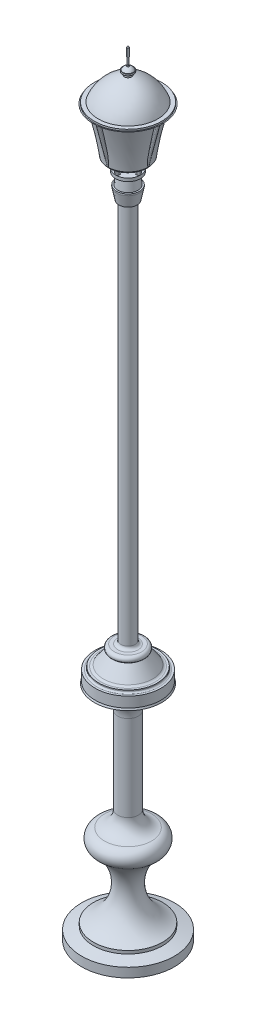
SolidWorks part; units mm, degrees
ref_plane "Front Plane" through (0, 0, 0) normal (0, 0, 1) x (1, 0, 0)
ref_plane "Top Plane" through (0, 0, 0) normal (0, 1, 0) x (1, 0, 0)
ref_plane "Right Plane" through (0, 0, 0) normal (1, 0, 0) x (0, 0, -1)
sketch "Sketch1" plane through (0, 0, 0) normal (0, 0, 1) x (1, 0, 0)
  line L0 (0, 0) -> (0, 250) construction
  line L1 (0, 0) -> (-15, 0)
  line L2 (-15, 0) -> (-15, 3)
  line L3 (-15, 3) -> (-11.1715, 4)
  line L4 (-11.1715, 4) -> (-11.1715, 5)
  line L5 (-3.3417, 64.4617) -> (-3.3417, 36.7043)
  line L6 (-10.8822, 72.0027) -> (-10.6514, 72.5731)
  line L7 (-10.6514, 72.5731) -> (-10.6514, 75.9363)
  line L8 (-10.6514, 75.9363) -> (-9.9773, 75.9363)
  line L9 (-9.4473, 76.4663) -> (-9.4473, 76.7932)
  line L10 (-9.4473, 76.7932) -> (-8.8027, 76.7932)
  line L11 (-5.0647, 81.2612) -> (-7.992, 77.2077)
  line L12 (-4.4341, 83.0374) -> (-3.3006, 83.0374)
  line L13 (-2.3006, 84.0374) -> (-2.3006, 207.5309)
  line L14 (-2.3006, 207.5309) -> (-2.9601, 207.5309)
  line L15 (-2.9601, 207.5309) -> (-3.73, 211.2793)
  line L16 (-3.73, 211.2793) -> (-3.73, 211.7765)
  line L17 (-3.73, 211.7765) -> (-3.236, 211.7765)
  line L18 (-3.236, 211.7765) -> (-2.8892, 215.4171)
  line L19 (-2.8892, 215.4171) -> (0, 215.4171)
  line L20 (0, 0) -> (0, 215.4171)
  arc A0 (-11.1715, 5) -> (-8.8506, 26.2034) centre (-16.0559, 16.2634) ccw
  arc A1 (-7.6215, 31.5849) -> (-3.3417, 36.7043) centre (-8.5434, 36.7043) ccw
  arc A2 (-7.6215, 31.5849) -> (-8.8506, 26.2034) centre (-7.0899, 28.6324) ccw
  arc A3 (-3.3417, 64.4617) -> (-10.8822, 72.0027) centre (-10.8826, 64.4617) ccw
  arc A4 (-3.3006, 83.0374) -> (-2.3006, 84.0374) centre (-3.3006, 84.0374) ccw
  arc A5 (-7.992, 77.2077) -> (-8.8027, 76.7932) centre (-8.8027, 77.7932) cw
  arc A6 (-9.4473, 76.4663) -> (-9.9773, 75.9363) centre (-9.9773, 76.4663) cw
  arc A7 (-4.4341, 83.0374) -> (-5.0647, 81.2612) centre (-4.4341, 82.0374) ccw
  dimension "D6" = 3
  dimension "D7" = 1
  dimension "D8" = 1
  dimension "D9" = 0.53
  dimension "D10" = 1
  dimension "D1" = 250
  dimension "D2" = 15
  dimension "D3" = 3
  dimension "D4" = 1
  dimension "D5" = 1
  dimension "D11" = 5
revolve "Revolve1" add sketch "Sketch1" angle 360 about L0
sketch "Sketch2" plane through (0, 215.4171, 0) normal (0, 1, 0) x (1, 0, 0)
  circle A0 centre (0, 0) radius 4
  dimension "D1" = 8
extrude "Boss-Extrude1" add sketch "Sketch2" along normal blind 1 contours A0
sketch "Sketch3" plane through (0, 0, 0) normal (1, 0, 0) x (0, 0, -1)
  line L0 (-4, 216.4171) -> (-2.9788, 216.4171)
  line L1 (-4, 216.4171) -> (-4.6212, 219.4171)
  line L2 (-2.9788, 216.4171) -> (-3.6, 219.4171)
  line L3 (-4.6212, 219.4171) -> (-3.6, 219.4171)
  line L4 (4, 216.4171) -> (-4, 216.4171) construction
  dimension "D1" = 3
  dimension "D2" = 1
extrude "Boss-Extrude2" add sketch "Sketch3" along normal mid plane 1 separate body
fillet "Fillet3" 2 edges at (0.5, 217.9171, 4.3106) (-0.5, 217.9171, 4.3106) type full round first side face at (0.5, 217.9171, 3.8) second side face at (-0.5, 217.9171, 3.8) middle face at (0, 217.9171, 4.3106)
pattern_circular "CirPattern1" count 4 over 360 about axis through (0, 216.4171, 0) along (0, 1, 0) of bodies 103
sketch "Sketch5" plane through (0, 0, 0) normal (0, 0, 1) x (1, 0, 0)
  line L0 (0, 253.7461) -> (0, 207.5309) construction
  line L1 (-2.3006, 207.5309) -> (2.3006, 207.5309) construction
  line L2 (0, 219.4171) -> (-6.1343, 219.4171)
  line L3 (0.5, 219.4171) -> (-0.5, 219.4171) construction
  line L4 (-6.1343, 219.4171) -> (-6.5254, 219.9171)
  line L5 (-6.5254, 219.9171) -> (-0.25, 219.9171)
  line L6 (-0.25, 219.9171) -> (-0.25, 229.4993)
  line L7 (-0.25, 229.4993) -> (-4.7112, 229.4993)
  line L8 (-4.7112, 229.4993) -> (-4.7053, 229.9993)
  line L9 (-4.7053, 229.9993) -> (-1.0202, 231.2834)
  line L10 (-1.0202, 231.2834) -> (-1.0202, 232.2834)
  line L11 (-1.0202, 232.2834) -> (-9.2643, 233.4416)
  line L12 (-9.2643, 233.4416) -> (-9.63, 233.9416)
  line L13 (-9.63, 233.9416) -> (-10.304, 233.9416)
  line L14 (-10.304, 233.9416) -> (-11.2392, 234.4416)
  line L15 (-11.2392, 234.4416) -> (-10.9002, 234.4416)
  line L16 (-10.9002, 234.4416) -> (-10.9002, 234.9755)
  line L17 (-10.9002, 234.9755) -> (-9.63, 234.9755)
  line L18 (-1.1341, 242.5002) -> (-1.1341, 243.5002)
  line L19 (-1.1341, 243.5002) -> (-1.7731, 243.5002)
  line L20 (-1.7731, 243.5002) -> (-1.7731, 244.0002)
  line L21 (-1.7731, 244.0002) -> (-1.6121, 244.0002)
  line L22 (-0.2008, 245.3942) -> (-0.2008, 247.5915)
  line L23 (-0.2008, 247.5915) -> (-0.2951, 247.5915)
  line L24 (-0.2951, 247.5915) -> (-0.2951, 250.2454)
  line L25 (-0.2951, 250.2454) -> (0, 250.6149)
  line L26 (0, 219.4171) -> (0, 250.6149)
  line L27 (-0.305, 244.9775) -> (-0.305, 245.3942)
  line L28 (-0.305, 245.3942) -> (-0.2008, 245.3942)
  arc A0 (-9.63, 234.9755) -> (-1.1341, 242.5002) centre (1.9974, 230.406) cw
  arc A1 (-1.6121, 244.0002) -> (-0.305, 244.9775) centre (0.1243, 243.0406) cw
  dimension "D1" = 0.5
  dimension "D2" = 0.5
  dimension "D3" = 0.5
  dimension "D4" = 0.5
  dimension "D5" = 1
  dimension "D6" = 0.5
  dimension "D8" = 0.5
  dimension "D9" = 1
revolve "Revolve2" add sketch "Sketch5" angle 360 about L0
sketch "Sketch6" plane through (0, 0, 0) normal (1, 0, 0) x (0, 0, -1)
  line L0 (-10.304, 233.9416) -> (-6.5254, 219.9171)
  line L1 (-10.304, 233.9416) -> (-9.399, 233.9416)
  line L2 (-6.5254, 219.9171) -> (-5.6203, 219.9171)
  line L3 (-9.399, 233.9416) -> (-5.6203, 219.9171)
  line L4 (-10.304, 233.9416) -> (10.304, 233.9416) construction
  line L6 (6.5254, 219.9171) -> (-6.5254, 219.9171) construction
extrude "Boss-Extrude4" add sketch "Sketch6" along normal mid plane 1 separate body contours L3 L2 L0 L1
fillet "Fillet6" 2 edges at (-0.5, 226.9294, 8.4147) (0.5, 226.9294, 8.4147) type full round first side face at (-0.5, 226.9294, 7.9622) second side face at (0.5, 226.9294, 7.9622) middle face at (0, 226.9294, 8.4147)
pattern_circular "CirPattern2" count 4 over 360 about axis through (0, 219.9171, 0) along (0, 1, 0) of bodies 108
surface "Surface-Loft1"
scale "Scale2" bodies to scale 112 109 102 110 107 111 108 scale about origin uniform scaling yes scale factor 0.5
scale "Scale3" bodies to scale 120 124 121 125 122 126 123 scale about origin uniform scaling yes scale factor 0.8
scale "Scale4" bodies to scale 127 128 132 133 129 130 131 scale about origin uniform scaling yes scale factor 0.8
scale "Scale5" bodies to scale 134 137 138 135 139 140 136 scale about origin uniform scaling yes scale factor 0.8
